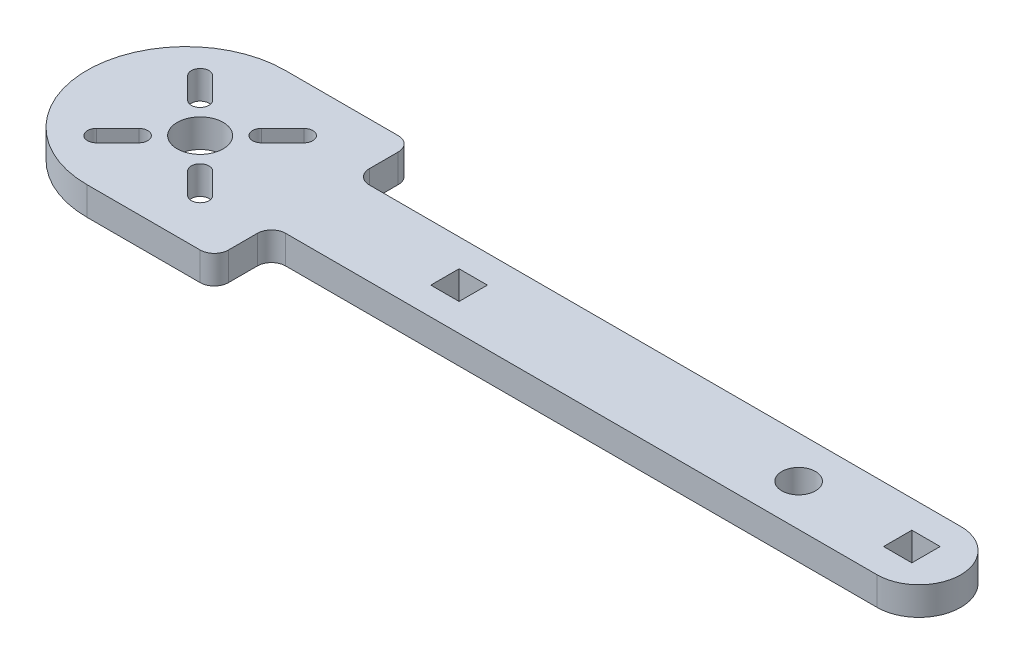
SolidWorks part; units mm, degrees
material "Thornel VCB-20 Carbon Cloth"
ref_plane "Front Plane" through (0, 0, 0) normal (0, 0, 1) x (1, 0, 0)
ref_plane "Top Plane" through (0, 0, 0) normal (0, 1, 0) x (1, 0, 0)
ref_plane "Right Plane" through (0, 0, 0) normal (1, 0, 0) x (0, 0, -1)
sketch "Sketch1" plane through (0, 0, 0) normal (0, 1, 0) x (1, 0, 0)
  line L0 (-58.0134, 7.2134) -> (-43.5866, -7.2134) construction
  line L1 (-50.8, 14) -> (-36.8, 14)
  line L2 (-50.8, 14) -> (-50.8, -14) construction
  line L3 (-50.8, -14) -> (-36.8, -14)
  line L7 (-58.4887, -7.6887) -> (-43.1113, 7.6887) construction
  line L8 (-58.1362, 7.3362) -> (-55.131, 4.331) construction
  line L9 (-57.2523, 8.2201) -> (-54.2471, 5.2149)
  line L10 (-59.0201, 6.4523) -> (-56.0149, 3.4471)
  line L11 (-43.4638, 7.3362) -> (-46.469, 4.331) construction
  line L12 (-42.5799, 6.4523) -> (-45.5851, 3.4471)
  line L13 (-44.3477, 8.2201) -> (-47.3529, 5.2149)
  line L14 (-43.4638, -7.3362) -> (-46.469, -4.331) construction
  line L15 (-44.3477, -8.2201) -> (-47.3529, -5.2149)
  line L16 (-42.5799, -6.4523) -> (-45.5851, -3.4471)
  line L17 (-58.1362, -7.3362) -> (-55.131, -4.331) construction
  line L18 (-59.0201, -6.4523) -> (-56.0149, -3.4471)
  line L19 (-57.2523, -8.2201) -> (-54.2471, -5.2149)
  line L21 (-34.8, 7.9146) -> (-34.8, 12)
  line L24 (-34.8, -12) -> (-34.8, -7.9146)
  line L32 (-32.8, 5.9146) -> (50.8, 5.9146)
  line L33 (-32.8, -5.9146) -> (50.8, -5.9146)
  line L34 (-50.8, 0) -> (50.8, 0) construction
  line L35 (-50.8, 14) -> (-52.8, 14)
  line L36 (-50.8, -14) -> (-52.8, -14)
  line L38 (47.8, -2) -> (51.8, -2)
  line L39 (47.8, -2) -> (47.8, 2)
  line L40 (47.8, 2) -> (51.8, 2)
  line L41 (51.8, -2) -> (51.8, 2)
  line L42 (47.8, -2) -> (51.8, 2) construction
  line L43 (47.8, 2) -> (51.8, -2) construction
  line L44 (-16.2, -2) -> (-12.2, -2)
  line L45 (-16.2, -2) -> (-16.2, 2)
  line L46 (-16.2, 2) -> (-12.2, 2)
  line L47 (-12.2, -2) -> (-12.2, 2)
  line L48 (-16.2, -2) -> (-12.2, 2) construction
  line L49 (-16.2, 2) -> (-12.2, -2) construction
  circle A2 centre (-50.8, 0) radius 3.25
  arc A3 (-57.2523, 8.2201) -> (-59.0201, 6.4523) centre (-58.1362, 7.3362) ccw
  arc A4 (-56.0149, 3.4471) -> (-54.2471, 5.2149) centre (-55.131, 4.331) ccw
  arc A5 (-42.5799, 6.4523) -> (-44.3477, 8.2201) centre (-43.4638, 7.3362) ccw
  arc A6 (-47.3529, 5.2149) -> (-45.5851, 3.4471) centre (-46.469, 4.331) ccw
  arc A7 (-44.3477, -8.2201) -> (-42.5799, -6.4523) centre (-43.4638, -7.3362) ccw
  arc A8 (-45.5851, -3.4471) -> (-47.3529, -5.2149) centre (-46.469, -4.331) ccw
  arc A9 (-59.0201, -6.4523) -> (-57.2523, -8.2201) centre (-58.1362, -7.3362) ccw
  arc A10 (-54.2471, -5.2149) -> (-56.0149, -3.4471) centre (-55.131, -4.331) ccw
  arc A12 (-34.8, -7.9146) -> (-32.8, -5.9146) centre (-32.8, -7.9146) cw
  arc A13 (-32.8, 5.9146) -> (-34.8, 7.9146) centre (-32.8, 7.9146) cw
  arc A14 (-36.8, -14) -> (-34.8, -12) centre (-36.8, -12) ccw
  arc A15 (-34.8, 12) -> (-36.8, 14) centre (-36.8, 12) ccw
  arc A16 (50.8, 5.9146) -> (50.8, -5.9146) centre (50.8, 0) cw
  arc A17 (-52.8, -14) -> (-52.8, 14) centre (-52.8, 0) cw
  circle A18 centre (33.8, 0) radius 2.3812
  point P0 (0, 0)
  point P12 (-50.8, 0)
  point P14 (-50.8, 0)
  point P17 (-56.6336, 5.8336)
  point P27 (-44.9664, 5.8336)
  point P34 (-44.9664, -5.8336)
  point P41 (-56.6336, -5.8336)
  point P46 (-50.8, 0)
  point P53 (-34.8, -7)
  point P56 (-34.8, 7)
  point P59 (-34.8, -14)
  point P62 (-34.8, 14)
  point P64 (49.8, 0)
  point P70 (-14.2, 0)
  dimension "D3" = 6.5
  dimension "D6" = 8.25
  dimension "D10" = 4.7625
  dimension "D17" = 2
  dimension "D18" = 2
  dimension "D16" = 5.9146
  dimension "D2" = 14
  dimension "D21" = 4
  dimension "D22" = 4
  dimension "D4" = 45
  dimension "D5" = 45
  dimension "D7" = 4.25
  dimension "D8" = 2.5
  dimension "D11" = 16
  dimension "D12" = 16
  dimension "D13" = 7
  dimension "D14" = 7
  dimension "D15" = 101.6
  dimension "D19" = 50.8
  dimension "D20" = 2
  dimension "D23" = 1
  dimension "D24" = 17
  dimension "D25" = 4
  dimension "D26" = 65
  dimension "D9" = 4
extrude "Boss-Extrude1" add sketch "Sketch1" along normal blind 4
